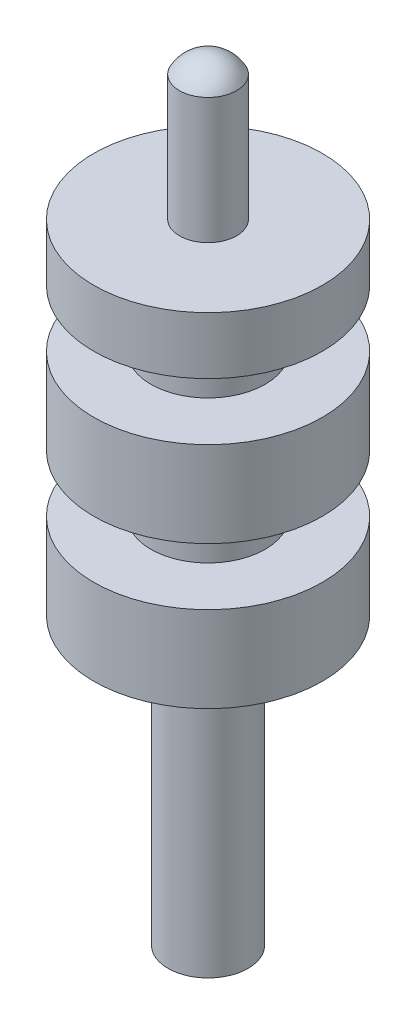
SolidWorks part; units mm, degrees
ref_plane "前视基准面" through (0, 0, 0) normal (0, 0, 1) x (1, 0, 0)
ref_plane "上视基准面" through (0, 0, 0) normal (0, 1, 0) x (1, 0, 0)
ref_plane "右视基准面" through (0, 0, 0) normal (1, 0, 0) x (0, 0, -1)
sketch "草图1" plane through (0, 0, 0) normal (0, 0, 1) x (1, 0, 0)
  line L0 (0, 0) -> (0, 13.2)
  line L1 (0, 13.2) -> (0.5, 13.2)
  line L2 (0.5, 13.2) -> (0.5, 11)
  line L3 (0.5, 11) -> (2, 11)
  line L4 (2, 11) -> (2, 10)
  line L5 (2, 10) -> (1, 10)
  line L6 (1, 10) -> (1, 9)
  line L7 (1, 9) -> (2, 9)
  line L8 (2, 9) -> (2, 7.5)
  line L9 (2, 7.5) -> (1, 7.5)
  line L11 (1, 0) -> (0, 0)
  line L12 (1, 7.5) -> (1, 6.5)
  line L13 (1, 6.5) -> (2, 6.5)
  line L14 (2, 6.5) -> (2, 5)
  line L15 (2, 5) -> (0.7, 5)
  line L16 (0.7, 5) -> (0.7, 0)
  line L17 (0.7, 0) -> (0, 0)
  point P14 (1.35, 5)
  dimension "D1" = 0.5
  dimension "D2" = 2.2
  dimension "D3" = 6
  dimension "D4" = 1
  dimension "D5" = 1
  dimension "D6" = 1.5
  dimension "D7" = 1
  dimension "D8" = 5
  dimension "D9" = 0.7
  dimension "D10" = 1
  dimension "D11" = 1
  dimension "D12" = 2
revolve "旋转2" add sketch "草图1" angle 360 about L0 region at (0.7192, 6.9562, 0)
sketch "草图2" plane through (0, 0, 0) normal (0, -1, 0) x (-1, 0, 0)
  circle A0 centre (0, 0) radius 0.5
  dimension "D1" = 1
extrude "切除-拉伸1" cut sketch "草图2" against normal blind 4 contours A0 | A0 region at (0, 0, 0)
dome "圆顶1" faces to dome 1 distance 0.3 reverse direction no elliptical dome no face at (0.5, 13.2, 0) parameters "D1"=0.3
